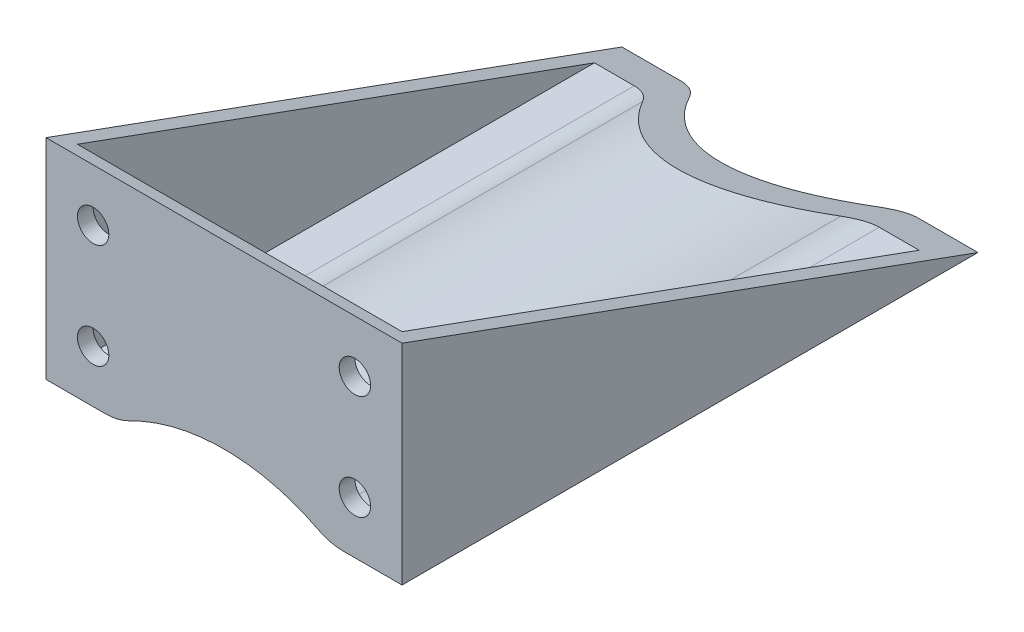
SolidWorks part; units mm, degrees
ref_plane "Alzado" through (0, 0, 0) normal (0, 0, 1) x (1, 0, 0)
ref_plane "Planta" through (0, 0, 0) normal (0, 1, 0) x (1, 0, 0)
ref_plane "Vista lateral" through (0, 0, 0) normal (1, 0, 0) x (0, 0, -1)
sketch "Croquis4" plane through (0, 0, 0) normal (1, 0, 0) x (0, 0, -1)
  line L0 (0, 0) -> (55, 0)
  line L1 (55, 0) -> (0, 20)
  line L2 (0, 20) -> (0, 0)
  dimension "D1" = 20
  dimension "D2" = 55
extrude "Saliente-Extruir3" add sketch "Croquis4" along normal blind 34
sketch "Croquis5" plane through (0, 0, 0) normal (0, 0, 1) x (1, 0, 0)
  line L0 (0, 0) -> (34, 20) construction
  line L2 (29.5, 5) -> (4.5, 5)
  line L3 (29.5, 5) -> (29.5, 15)
  line L4 (29.5, 15) -> (4.5, 15)
  line L5 (4.5, 5) -> (4.5, 15)
  line L6 (29.5, 5) -> (4.5, 15) construction
  line L7 (29.5, 15) -> (4.5, 5) construction
  circle A0 centre (4.5, 15) radius 1.5
  circle A1 centre (29.5, 15) radius 1.5
  circle A2 centre (29.5, 5) radius 1.5
  circle A3 centre (4.5, 5) radius 1.5
  point P4 (17, 10)
  dimension "D3" = 2
  dimension "D1" = 25
  dimension "D2" = 10
  dimension "D4" = 2
sketch "Croquis6" plane through (0, 0, 0) normal (0, 0, 1) x (1, 0, 0)
  line L0 (17, 0) -> (17, -17) construction
  line L1 (34, 0) -> (0, 0) construction
  circle A0 centre (17, -17) radius 19.75
  dimension "D1" = 39.5
  dimension "D2" = 17
extrude "Cortar-Extruir2" cut sketch "Croquis6" against normal through all
shell "Vaciado3" thickness 1.5 removed face at (17, 7.125, -35.4062)
extrude "Cortar-Extruir3" cut sketch "Croquis5" against normal blind 10 contours A0 | A1 | A2 | A3
fillet "Redondeo1" radius 5 2 edges at (6.947, 0, -27.5) (27.053, 0, -27.5)
fillet "Redondeo3" radius 5 2 edges at (27.4553, 1.5, -26.1875) (6.5447, 1.5, -26.1875)
